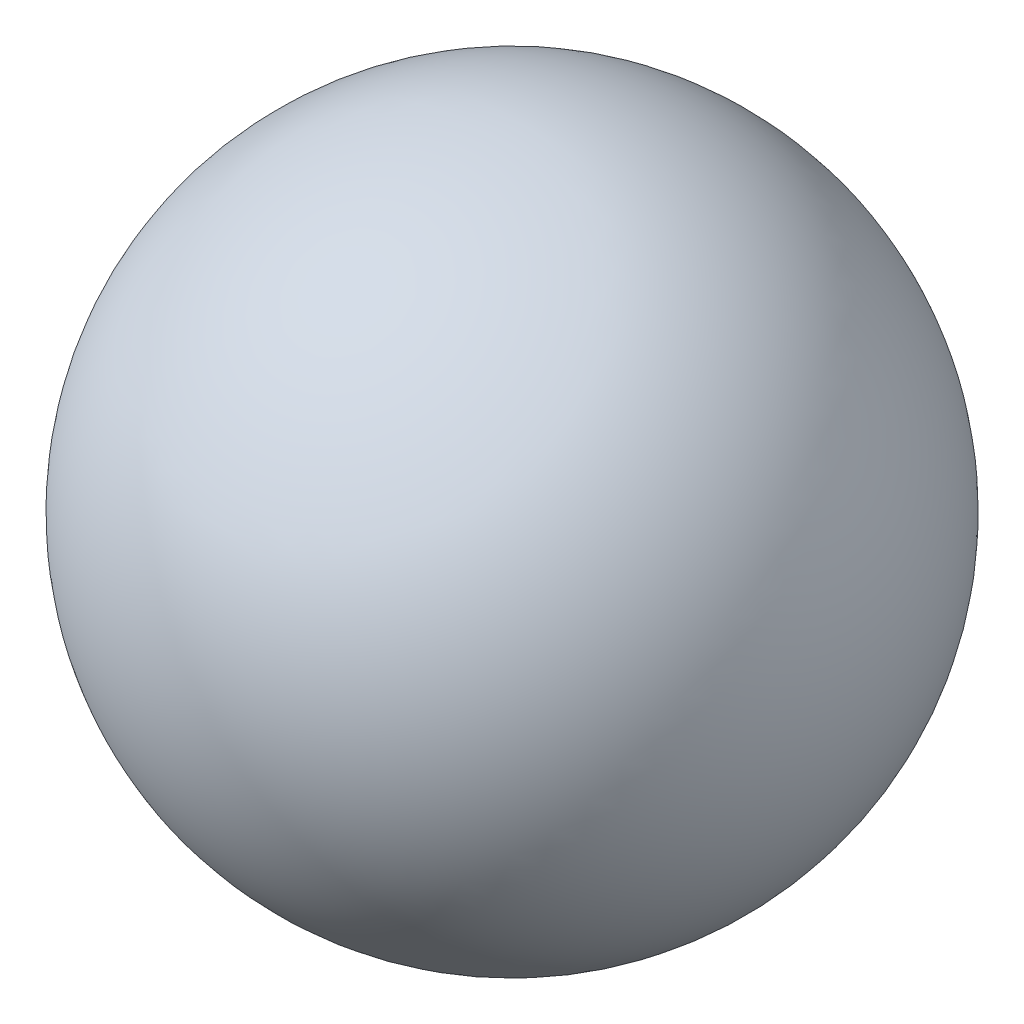
SolidWorks part; units mm, degrees
ref_plane "前视基准面" through (0, 0, 0) normal (0, 0, 1) x (1, 0, 0)
ref_plane "上视基准面" through (0, 0, 0) normal (0, 1, 0) x (1, 0, 0)
ref_plane "右视基准面" through (0, 0, 0) normal (1, 0, 0) x (0, 0, -1)
sketch "草图1" plane through (0, 0, 0) normal (0, 1, 0) x (1, 0, 0)
  line L0 (0, -10) -> (0, 10) construction
  circle A0 centre (0, 0) radius 10
  point P3 (-2.1698, 0)
  point P6 (0, 0)
  point P7 (0, 1.25)
  point P8 (0, -1.25)
  point P10 (-1.25, 0)
  dimension "D1" = 20
revolve "旋转33" add sketch "草图1" angle 360 about L0 region at (-4.2441, 0, 0)
